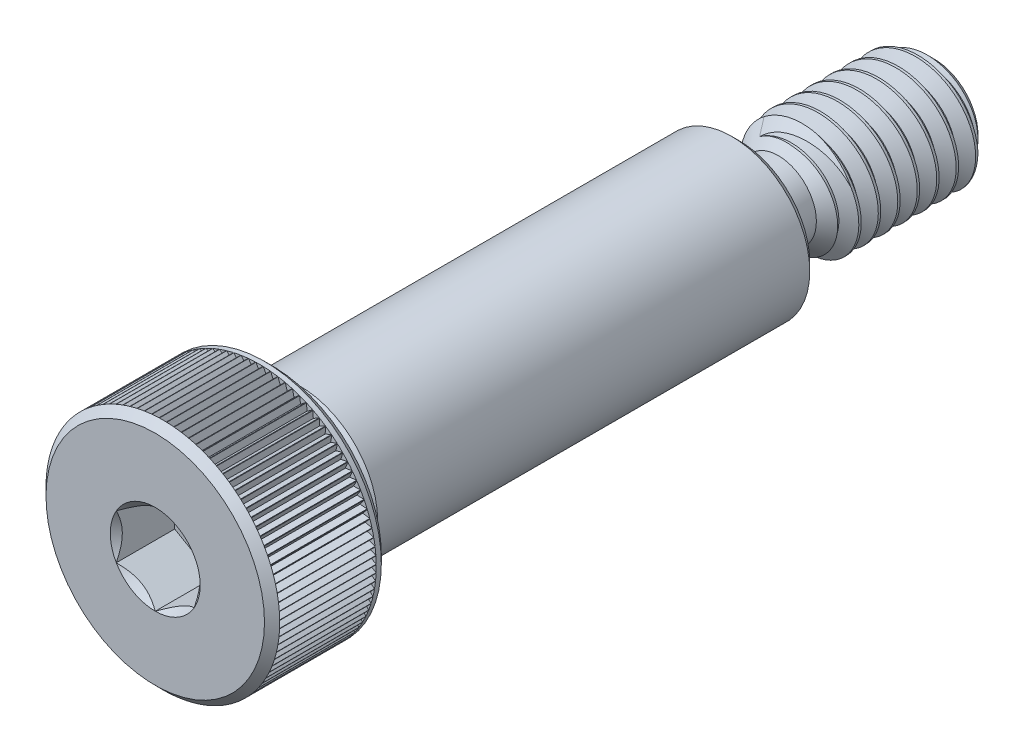
SolidWorks part; units mm, degrees
ref_plane "Front Plane" through (0, 0, 0) normal (0, 0, 1) x (1, 0, 0)
ref_plane "Top Plane" through (0, 0, 0) normal (0, 1, 0) x (1, 0, 0)
ref_plane "Right Plane" through (0, 0, 0) normal (1, 0, 0) x (0, 0, -1)
sketch "Sketch1" plane through (0, 0, 0) normal (1, 0, 0) x (0, 0, -1)
  line L0 (-10, 0) -> (10, 0) construction
  line L1 (-10, -3) -> (-10, 3) construction
  line L2 (-10, 3) -> (-7, 3) construction
  line L3 (-7, 3) -> (-7, 1.797) construction
  line L4 (-7, 1.797) -> (-6.492, 1.797) construction
  line L5 (-6.492, 1.797) -> (-6.289, 2) construction
  line L6 (-6.289, 2) -> (5, 2) construction
  line L7 (9.9688, 1.5541) -> (10.2188, 1.1211) construction
  line L8 (10.2188, 1.1211) -> (10.4688, 1.5541) construction
  line L9 (10, -1.5) -> (10, 1.5) construction
  line L10 (5, 2) -> (10, 2) construction
  line L11 (10.4688, 1.5541) -> (9.9688, 1.5541) construction
  line L12 (10.2187, 1.5541) -> (10.2188, 1.5) construction
  line L13 (10.2188, 1.1211) -> (10.2188, 1.1752) construction
  line L14 (10.25, 1.1752) -> (10.1875, 1.1752) construction
  line L15 (10.4375, 1.5) -> (10, 1.5) construction
  line L16 (10.2188, 1.5271) -> (10.4531, 1.5271) construction
  line L17 (10.2188, 1.5271) -> (9.9844, 1.5271) construction
  line L18 (-10, 2.805) -> (-9.805, 3) construction
  line L19 (-7.195, 3) -> (-7, 2.805) construction
  line L20 (10, 1.5) -> (5, 1.5) construction
  line L21 (9.625, 1.5) -> (10, 1.125) construction
  line L22 (6.525, 1.5) -> (6, 0.975) construction
  line L23 (6, 0.975) -> (5.2625, 0.975) construction
  line L24 (5, 1.5) -> (5, 1.2375) construction
  line L25 (-8.5, 1) -> (-8.5, -1) construction
  line L26 (-8.5, -1) -> (-10, -1) construction
  line L27 (-8.5, 1) -> (-10, 1) construction
  line L28 (-9.805, 0) -> (-7.3255, 0) construction
  arc A0 (5, 1.2375) -> (5.2625, 0.975) centre (5.2625, 1.2375) ccw construction
  point P4 (0, 0)
  point P7 (-10, 0)
  point P18 (10, 0)
  point P25 (8.25, -1.5)
  point P38 (-8.5, 3)
  point P45 (-8.5, 0)
  point P46 (6.2625, 1.2375)
  point P48 (-6.492, 0)
  point P51 (-8.5, 0)
  point P52 (5, 0)
  dimension "Head Diameter" = 6
  dimension "Head Height" = 3
  dimension "Thread Diameter" = 3
  dimension "Shoulder Diameter" = 4
  dimension "Thread Length" = 5
  dimension "D1" = 0.508
  dimension "D2" = 135
  dimension "D3" = 0.203
  dimension "Shoulder Length" = 12
  dimension "Thread Pitch" = 0.5
  dimension "D4" = 0.0625
  dimension "D5" = 1.75
  dimension "D6" = 0.195
  dimension "D7" = 0.375
  dimension "D8" = 1.95
  dimension "D9" = 1
  dimension "Drive Size" = 2
  dimension "Knurling Length" = 2.4795
sketch "Sketch3" plane through (0, 0, 0) normal (1, 0, 0) x (0, 0, -1)
  line L0 (-10, 0) -> (-10, 2.805)
  line L1 (-10, -3) -> (-10, 3) construction
  line L2 (-10, 2.805) -> (-9.805, 3)
  line L3 (-9.805, 3) -> (-7.195, 3)
  line L4 (-7.195, 3) -> (-7, 2.805)
  line L5 (-7, 2.805) -> (-7, 1.797)
  line L6 (-7, 1.797) -> (-6.492, 1.797)
  line L7 (-6.492, 1.797) -> (-6.289, 2)
  line L8 (-6.289, 2) -> (5, 2)
  line L9 (5, 2) -> (5, 1.2375)
  line L10 (5.2625, 0.975) -> (6, 0.975)
  line L11 (6, 0.975) -> (6.525, 1.5)
  line L12 (6.525, 1.5) -> (9.625, 1.5)
  line L13 (9.625, 1.5) -> (10, 1.125)
  line L14 (10, 1.125) -> (10, 0)
  line L15 (10, 0) -> (-10, 0)
  arc A0 (5, 1.2375) -> (5.2625, 0.975) centre (5.2625, 1.2375) ccw construction
  arc A1 (5, 1.2375) -> (5.2625, 0.975) centre (5.2625, 1.2375) ccw
revolve "Revolve1" add sketch "Sketch3" angle 360 about L0
sketch "Sketch4" plane through (0, 0, 0) normal (0, 0, 1) x (1, 0, 0)
  line L0 (0, -3) -> (0, 3) construction
  line L1 (0, 1.1547) -> (-1, 0.5774)
  line L2 (-1, 0.5774) -> (-1, -0.5774)
  line L3 (-1, -0.5774) -> (0, -1.1547)
  line L4 (0, -1.1547) -> (1, -0.5774)
  line L5 (1, -0.5774) -> (1, 0.5774)
  line L6 (1, 0.5774) -> (0, 1.1547)
  circle A0 centre (0, 0) radius 1 construction
extrude "Cut-Extrude1" cut sketch "Sketch4" against normal up to vertex (-8.5 mm away) from vertex up to point (0, 0, 8.5) starting at point (0, 0, 10)
sketch "Sketch5" plane through (0, 0, 0) normal (0, 0, 1) x (1, 0, 0)
  line L0 (0, -3) -> (0, 3) construction
  circle A0 centre (0, 0) radius 1.1547
extrude "Cut-Extrude2" cut sketch "Sketch5" against normal up to vertex (-8.5 mm away) draft 45 from vertex up to point (0, 0, 8.5) starting at point (0, 0, 10)
chamfer "Chamfer1" distance 0.195 angle 45 1 edges at (2, 0, -5)
sketch "Sketch6" plane through (0, 0, -10) normal (0, 0, -1) x (-1, 0, 0)
  circle A0 centre (0, 0) radius 1.5
curve "Helix/Spiral1" pitch 0.5 height 4.75 radius 1.5 centre (0, 0, -10) axis (0, 0, 1) start towards (0, 1, 0)
ref_plane "Plane1" through (0, 0, -6) normal (0, 0, 1) x (1, 0, 0)
split "Split1" trim tools "Plane1" bodies to split 106 resulting bodies 110 111
sketch "Sketch7" plane through (0, 0, 0) normal (1, 0, 0) x (0, 0, -1)
  line L0 (9.9844, 1.5271) -> (10.1875, 1.1752)
  line L1 (10.1875, 1.1752) -> (10.25, 1.1752)
  line L2 (10.25, 1.1752) -> (10.4531, 1.5271)
  line L3 (10.4531, 1.5271) -> (9.9844, 1.5271)
sweep "Cut-Sweep1" cut profiles "Sketch7" path "Helix/Spiral1" align with end faces yes
combine bodies "Combine1" operation type add bodies to combine 110 107
sketch "Sketch8" plane through (0, 0, 0) normal (0, 0, 1) x (1, 0, 0)
  line L0 (0, 3) -> (0, 0) construction
  line L1 (-0.0901, 3) -> (0.0901, 3)
  line L2 (0.0901, 3) -> (0, 2.844)
  line L3 (0, 2.844) -> (-0.0901, 3)
  line L4 (-0.0901, 3) -> (0, 0) construction
  line L5 (0, 0) -> (0.0901, 3) construction
  circle A0 centre (0, 0) radius 2.844 construction
  point P8 (0, 3)
  dimension "D1" = 0.156
  dimension "D2" = 3.439
extrude "Cut-Extrude3" cut sketch "Sketch8" against normal up to vertex (-7.3255 mm away) from vertex up to point (0, 0, 7.3255) starting at point (0, 0, 9.805)
pattern_circular "CirPattern1" count 99 over 360 about axis through (0, 0, 10) along (0, 0, -1) of "Cut-Extrude3"
equation "\"D4@Sketch1\"=\"Thread Pitch@Sketch1\"/8"
equation "\"D5@Sketch1\"=\"Thread Pitch@Sketch1\"*3.5"
equation "\"D6@Sketch1\"=\"Head Diameter@Sketch1\"*.0325"
equation "\"D7@Sketch1\"=\"Thread Pitch@Sketch1\"*.75"
equation "\"D8@Sketch1\"=\"Thread Diameter@Sketch1\"*.65"
equation "\"D9@Sketch1\"=\"Thread Length@Sketch1\"*.2"
equation "\"D1@Chamfer1\"=\"D6@Sketch1\""
equation "\"D4@Helix/Spiral1\"=\"Thread Pitch@Sketch1\""
equation "\"D3@Helix/Spiral1\"=\"Thread Length@Sketch1\"*.95"
equation "\"D1@Sketch8\"=\"D6@Sketch1\"*.8"
equation "\"D1@CirPattern1\"=(360/\"D2@Sketch8\")-6"
equation "\"D1\"= \"D11@Sketch1\""
